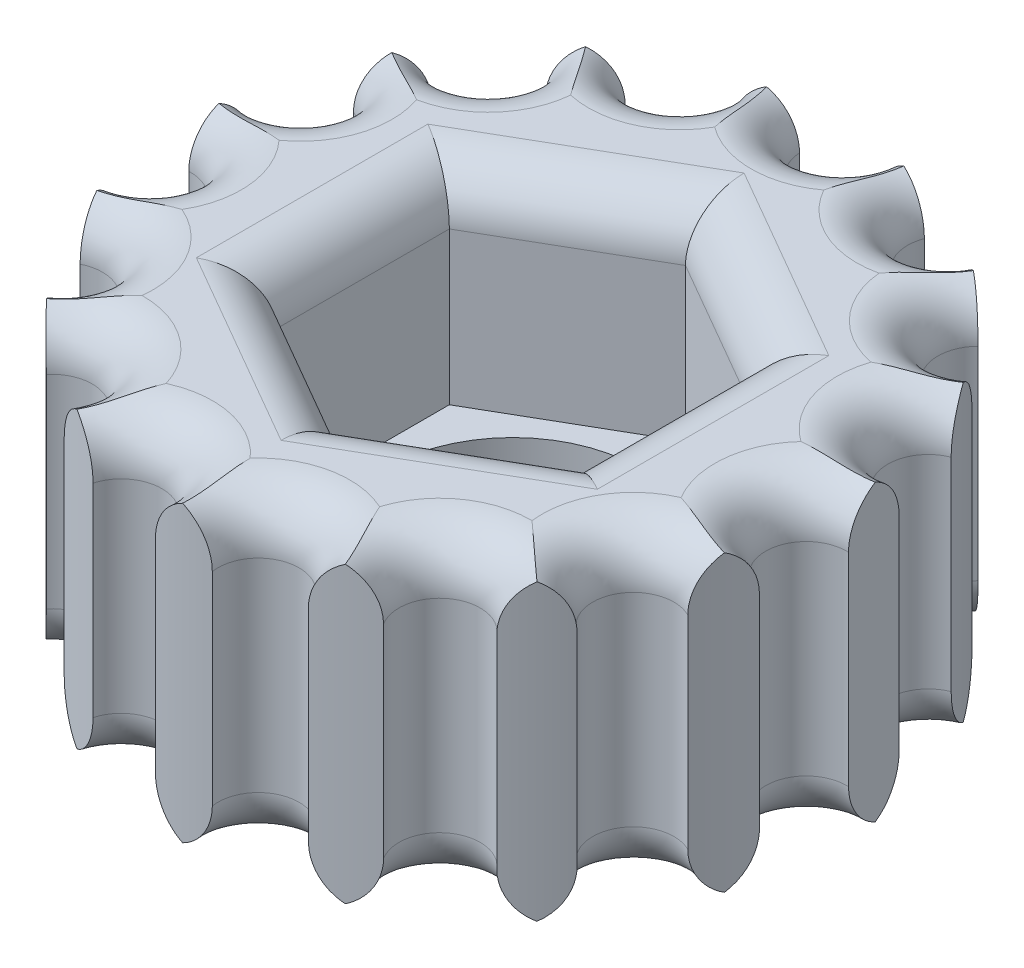
SolidWorks part; units mm, degrees
ref_plane "Front Plane" through (0, 0, 0) normal (0, 0, 1) x (1, 0, 0)
ref_plane "Top Plane" through (0, 0, 0) normal (0, 1, 0) x (1, 0, 0)
ref_plane "Right Plane" through (0, 0, 0) normal (1, 0, 0) x (0, 0, -1)
sketch "Sketch1" plane through (0, 0, 0) normal (0, 1, 0) x (1, 0, 0)
  line L0 (0, 3.4064) -> (-2.95, 1.7032)
  line L1 (-2.95, 1.7032) -> (-2.95, -1.7032)
  line L2 (-2.95, -1.7032) -> (0, -3.4064)
  line L3 (0, -3.4064) -> (2.95, -1.7032)
  line L4 (2.95, 1.7032) -> (2.95, -1.7032)
  line L5 (0, 3.4064) -> (2.95, 1.7032)
  circle A0 centre (0, 0) radius 6.5
  circle A1 centre (0, 0) radius 2.62 construction
  circle A2 centre (0, 0) radius 2.5
  circle A3 centre (0, 6.5) radius 1
sketch "Sketch2" plane through (0, 0, 0) normal (0, 1, 0) x (1, 0, 0)
  circle A0 centre (0, 0) radius 6.5 construction
  circle A1 centre (0, 0) radius 6.5
  circle A2 centre (0, 0) radius 2.5 construction
  circle A3 centre (0, 0) radius 2.5
extrude "Boss-Extrude1" add sketch "Sketch2" along normal blind 6
sketch "Sketch3" plane through (0, 6, 0) normal (0, 1, 0) x (1, 0, 0)
  line L0 (0, 3.4064) -> (-2.95, 1.7032) construction
  line L1 (-2.95, 1.7032) -> (-2.95, -1.7032) construction
  line L2 (-2.95, -1.7032) -> (0, -3.4064) construction
  line L3 (0, -3.4064) -> (2.95, -1.7032) construction
  line L4 (2.95, 1.7032) -> (2.95, -1.7032) construction
  line L5 (0, 3.4064) -> (2.95, 1.7032) construction
  line L6 (0, 3.4064) -> (-2.95, 1.7032)
  line L7 (-2.95, 1.7032) -> (-2.95, -1.7032)
  line L8 (-2.95, -1.7032) -> (0, -3.4064)
  line L9 (0, -3.4064) -> (2.95, -1.7032)
  line L10 (2.95, 1.7032) -> (2.95, -1.7032)
  line L11 (0, 3.4064) -> (2.95, 1.7032)
extrude "Cut-Extrude1" cut sketch "Sketch3" against normal blind 4
sketch "Sketch4" plane through (0, 6, 0) normal (0, 1, 0) x (1, 0, 0)
  circle A0 centre (0, 6.5) radius 1 construction
  circle A1 centre (0, 6.5) radius 1 construction
  circle A2 centre (0, 6.5) radius 0.8
  dimension "D1" = 0.2
extrude "Cut-Extrude2" cut sketch "Sketch4" against normal through all both and the other way through all
pattern_circular "CirPattern1" count 15 over 360 about axis through (0, 2, 0) along (0, -1, 0) of "Cut-Extrude2"
fillet "Fillet1" radius 1 37 edges at (0, 0, 2.5) (2.3184, 0, -5.2072) (0, 0, -5.7) (-2.3184, 0, -5.2072) (-4.2359, 0, -3.814) (-5.421, 0, -1.7614) (-5.6688, 0, 0.5958) (-4.9363, 0, 2.85) (-3.3504, 0, 4.6114) (-1.1851, 0, 5.5754) (1.1851, 0, 5.5754) (3.3504, 0, 4.6114) (4.9363, 0, 2.85) (5.6688, 0, 0.5958) (5.421, 0, -1.7614) (4.2359, 0, -3.814) (-1.475, 6, -2.5548) (-2.95, 6, 0) (-1.475, 6, 2.5548) (1.475, 6, 2.5548) (2.95, 6, 0) (1.475, 6, -2.5548) (5.421, 6, -1.7614) (5.6688, 6, 0.5958) (4.9363, 6, 2.85) (3.3504, 6, 4.6114) (1.1851, 6, 5.5754) (-1.1851, 6, 5.5754) (-3.3504, 6, 4.6114) (-4.9363, 6, 2.85) (-5.6688, 6, 0.5958) (-5.421, 6, -1.7614) (-4.2359, 6, -3.814) (-2.3184, 6, -5.2072) (0, 6, -5.7) (2.3184, 6, -5.2072) (4.2359, 6, -3.814)
